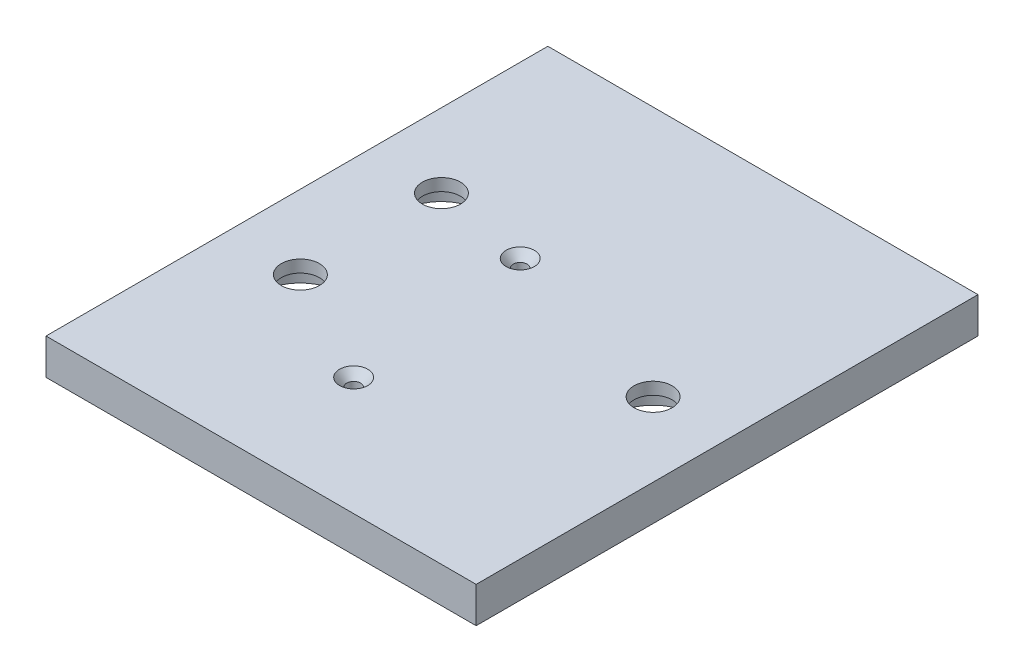
SolidWorks part; units mm, degrees
material "6061-T4 (SS)"
ref_plane "Front Plane" through (0, 0, 0) normal (0, 0, 1) x (1, 0, 0)
ref_plane "Top Plane" through (0, 0, 0) normal (0, 1, 0) x (1, 0, 0)
ref_plane "Right Plane" through (0, 0, 0) normal (1, 0, 0) x (0, 0, -1)
sketch "Sketch1" plane through (0, 0, 0) normal (0, 1, 0) x (1, 0, 0)
  line L1 (0, 0) -> (76.2, 0)
  line L2 (0, 0) -> (0, 88.9)
  line L3 (0, 88.9) -> (76.2, 88.9)
  line L4 (76.2, 0) -> (76.2, 88.9)
  dimension "D1" = 76.2
  dimension "D2" = 88.9
extrude "Boss-Extrude1" add sketch "Sketch1" along normal blind 6.35
hole_wizard "CSK for #2 Flat Head Socket Cap Screw1" positions "Sketch4" profile "Sketch5" countersink size "#2" standard "ANSI Inch"
sketch "Sketch4" plane through (0, 6.35, 0) normal (0, 1, 0) x (1, 0, 0)
  circle A0 centre (33.6, 20.9) radius 0.889 construction
  circle A1 centre (30.1, 53.9) radius 0.889 construction
  point P0 (33.6, 20.9)
  point P2 (30.1, 53.9)
sketch "Sketch5" plane through (33.6, 6.35, -20.9) normal (1, 0, 0) x (0, 0, 1)
  line L0 (0, 0) -> (0, 7.1326)
  line L1 (0, 7.1326) -> (1.2192, 6.4)
  line L2 (1.2192, 6.4) -> (1.2192, 1.4756)
  line L3 (1.2192, 1.4756) -> (2.5019, 0)
  line L5 (2.5019, 0) -> (0, 0)
  line L6 (-1.2192, 1.4756) -> (-2.5019, 0) construction
  line L10 (0, 7.1326) -> (-1.2192, 6.4) construction
  line L11 (0, -6.35) -> (0, 107.95) construction
  dimension "Hole Dia." = 2.4384
  dimension "Hole Depth" = 6.4
  dimension "Near C'Sink Dia." = 5.0038
  dimension "Near C'Sink Angle" = 82
  dimension "Drill Angle" = 118
sketch "Sketch6" plane through (0, 6.35, 0) normal (0, 1, 0) x (1, 0, 0)
  line L0 (30.1, 20.9) -> (30.1, 53.9) construction
  line L1 (30.1, 20.9) -> (33.6, 20.9) construction
  point P4 (30.1, 43.9)
  dimension "D1" = 10
sketch "Sketch7" plane through (0, 0, 0) normal (0, -1, 0) x (1, 0, 0)
  line L0 (38.1, 0) -> (38.1, -88.9) construction
  line L3 (0, 0) -> (76.2, 0) construction
  line L4 (76.2, -88.9) -> (0, -88.9) construction
  point P6 (38.1, -44.45)
hole_wizard "CBORE for 1/4 Binding Head Machine Screw1" positions "Sketch8" profile "Sketch9" counterbore size "1/4" standard "ANSI Inch"
sketch "Sketch8" plane through (0, 0, 0) normal (0, -1, 0) x (-1, 0, 0)
  circle A0 centre (-13.1064, 31.9532) radius 3.302 construction
  circle A1 centre (-13.1064, 56.9468) radius 3.302 construction
  circle A2 centre (-63.0936, 44.45) radius 3.302 construction
  point P0 (-63.0936, 44.45)
  point P2 (-13.1064, 31.9532)
  point P4 (-13.1064, 56.9468)
sketch "Sketch9" plane through (63.0936, 0, -44.45) normal (1, 0, 0) x (0, 0, -1)
  line L0 (0, 0) -> (0, 8.4298)
  line L1 (0, 8.4298) -> (3.3782, 6.4)
  line L2 (3.3782, 6.4) -> (3.3782, 4.191)
  line L3 (3.3782, 4.191) -> (7.1437, 4.191)
  line L4 (7.1437, 4.191) -> (7.1437, 0)
  line L5 (7.1437, 0) -> (0, 0)
  line L10 (0, 8.4298) -> (-3.3782, 6.4) construction
  line L11 (0, -6.35) -> (0, 107.95) construction
  dimension "Hole Dia." = 6.7564
  dimension "Hole Depth" = 6.4
  dimension "C'Bore Dia." = 14.2875
  dimension "C'Bore Depth" = 4.191
  dimension "Drill Angle" = 118
